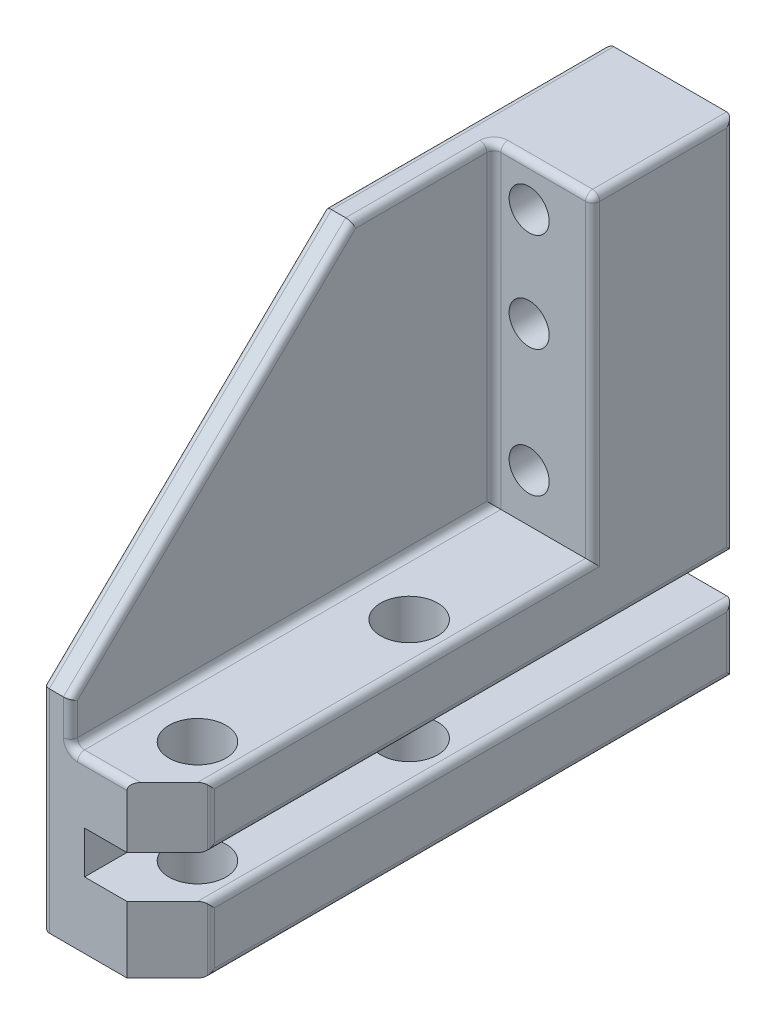
SolidWorks part; units mm, degrees
ref_plane "Front Plane" through (0, 0, 0) normal (0, 0, 1) x (1, 0, 0)
ref_plane "Top Plane" through (0, 0, 0) normal (0, 1, 0) x (1, 0, 0)
ref_plane "Right Plane" through (0, 0, 0) normal (1, 0, 0) x (0, 0, -1)
sketch "Sketch1" plane through (0, 0, 0) normal (0, 0, 1) x (1, 0, 0)
  line L1 (0, 0) -> (9, 0)
  line L2 (0, 0) -> (0, 34.4)
  line L3 (0, 34.4) -> (9, 34.4)
  line L4 (9, 0) -> (9, 34.4)
  circle A0 centre (4.5, 24.4) radius 1.42
  circle A1 centre (4.5, 15.4) radius 1.42
  circle A2 centre (4.5, 31.4) radius 1.42
  dimension "D3" = 2.84
  dimension "D7" = 2.84
  dimension "D8" = 7
  dimension "D1" = 9
  dimension "D2" = 34.4
  dimension "D4" = 4.5
  dimension "D5" = 9
  dimension "D6" = 10
extrude "Boss-Extrude1" add sketch "Sketch1" along normal blind 40 contours L1 L4 L3 L2 A1 A0 | A0 | A1 | A2 region at (0.3556, 17.2, 0) region at (4.5, 24.4, 0) region at (4.5, 15.4, 0)
extrude "Cut-Extrude1" cut sketch "Sketch1<3>" along normal blind 10 contours A0 | A2 | A1 region at (4.5, 24.4, 0) region at (4.5, 31.4, 0)
sketch "Sketch1<3>" plane through (0, 0, 0) normal (0, 0, 1) x (1, 0, 0) same geometry as "Sketch1"
sketch "Sketch2" plane through (9, 0, 0) normal (1, 0, 0) x (0, 0, -1)
  line L0 (0, 0) -> (0, 34.4) construction
  line L1 (0, 4.7) -> (-40, 4.7)
  line L2 (0, 4.7) -> (0, 7.7)
  line L3 (0, 7.7) -> (-40, 7.7)
  line L4 (-40, 4.7) -> (-40, 7.7)
  line L5 (-40, 0) -> (-40, 34.4) construction
  line L6 (-40, 0) -> (0, 0) construction
  dimension "D1" = 3
  dimension "D2" = 7.7
extrude "Cut-Extrude2" cut sketch "Sketch2" against normal blind 6
sketch "Sketch3" plane through (9, 0, 0) normal (1, 0, 0) x (0, 0, -1)
  line L0 (-20, 34.4) -> (-40, 15)
  line L1 (-40, 34.4) -> (0, 34.4) construction
  line L2 (-40, 7.7) -> (-40, 34.4) construction
  line L3 (-40, 0) -> (0, 0) construction
  line L4 (0, 0) -> (0, 34.4) construction
  line L5 (-40, 15) -> (-48.3794, 51.9132)
  line L6 (-48.3794, 51.9132) -> (-20, 34.4)
  dimension "D1" = 15
  dimension "D2" = 20
extrude "Cut-Extrude3" cut sketch "Sketch3" against normal up to surface (9 mm away) up to face at (0, 17.2, 20)
sketch "Sketch4" plane through (0, 0, 0) normal (-1, 0, 0) x (0, 0, 1)
  line L0 (15, 34.4) -> (15, 4.4)
  line L1 (20, 34.4) -> (0, 34.4) construction
  line L2 (15, 4.4) -> (-9.525, 4.4)
  line L3 (-9.525, 4.4) -> (-9.525, 34.4)
  line L4 (-9.525, 34.4) -> (15, 34.4)
  line L6 (0, 0) -> (0, 34.4) construction
  line L7 (0, 0) -> (0, 34.4) construction
  dimension "D1" = 30
  dimension "D2" = 15
  dimension "D3" = 9.525
sketch "Sketch5" plane through (9, 0, 0) normal (-1, 0, 0) x (0, 0, 1)
  line L0 (10, 34.4) -> (10, 12)
  line L1 (10, 12) -> (40, 12)
  line L5 (40, 15) -> (20, 34.4)
  line L6 (20, 34.4) -> (0, 34.4)
  line L7 (0, 34.4) -> (0, 0)
  line L8 (0, 0) -> (40, 0)
  line L9 (40, 0) -> (40, 15)
  line L10 (40, 15) -> (20, 34.4)
  line L11 (20, 34.4) -> (0, 34.4)
  line L12 (0, 34.4) -> (0, 0)
  line L13 (0, 0) -> (40, 0)
  line L14 (40, 0) -> (40, 15)
  line M18 (0, 34.4) -> (20, 34.4)
  line M19 (20, 34.4) -> (40, 15)
  line M20 (40, 15) -> (40, 7.7)
  dimension "D2" = 10
  dimension "D3" = 12
  dimension "D1" = 0
extrude "Cut-Extrude6" cut sketch "Sketch5" along normal blind 7 contours L1 L0 M18 M19 M20 region at (9, 21.2789, 21.6179)
sketch "Sketch6" plane through (0, 0, 0) normal (0, -1, 0) x (1, 0, 0)
  line L0 (0, 40) -> (9, 40) construction
  line L1 (9, 40) -> (9, 0) construction
  circle A0 centre (6, 35) radius 2.0193
  circle A1 centre (6, 20) radius 2.0193
  dimension "D1" = 4.0386
  dimension "D4" = 3
  dimension "D2" = 15
  dimension "D3" = 5
extrude "Cut-Extrude5" cut sketch "Sketch6" against normal blind 20
fillet "Fillet2" radius 0.5 5 edges at (0, 34.4, 10) (0, 24.7, 30) (0, 7.5, 40) (0, 0, 20) (0, 17.2, 0)
chamfer "Chamfer4" distance 3 angle 45 2 edges at (9, 2.35, 40) (9, 9.85, 40)
fillet "Fillet3" radius 0.5 17 edges at (9, 2.35, 0) (9, 0, 18.5) (9, 2.35, 37) (9, 4.7, 18.5) (9, 23.2, 10) (9, 34.4, 5) (9, 21.05, 0) (9, 7.7, 18.5) (9, 9.85, 37) (9, 12, 23.5) (4, 12, 40) (5.5, 34.4, 10) (2, 13.5, 40) (2, 24.7, 30) (2, 34.4, 15) (2, 23.2, 10) (2, 12, 25)
